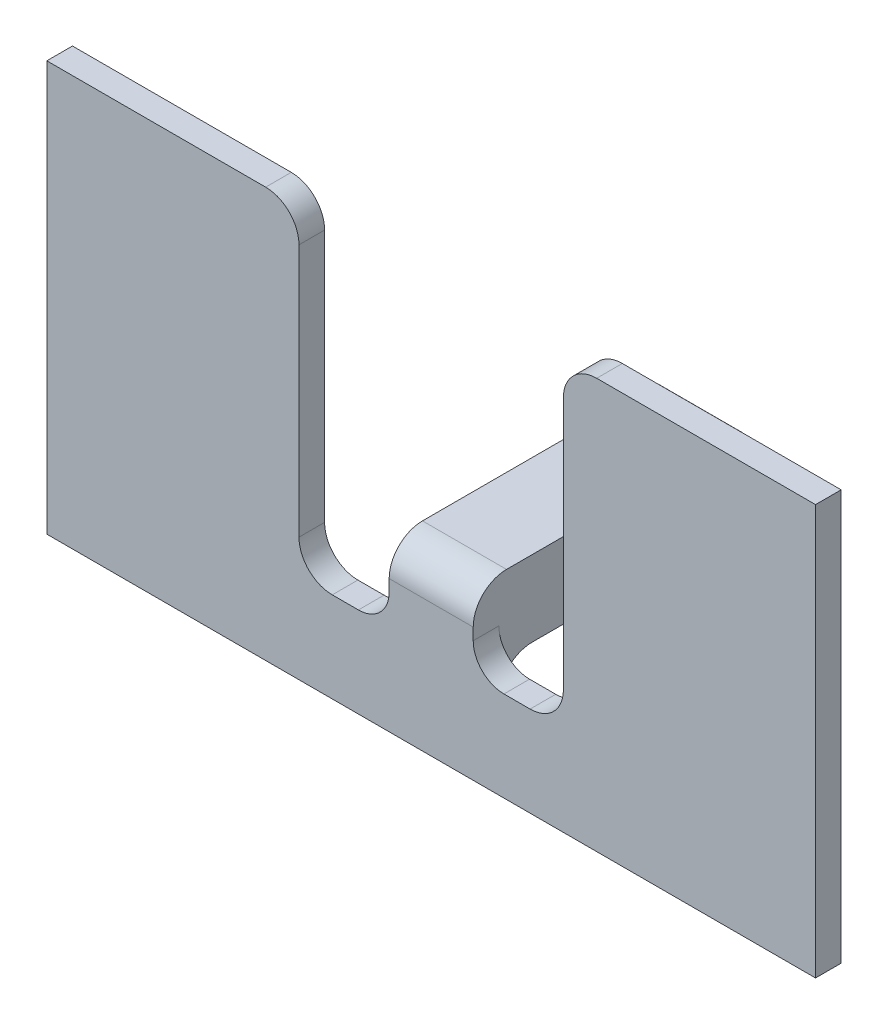
SolidWorks part; units mm, degrees
ref_plane "Front Plane" through (0, 0, 0) normal (0, 0, 1) x (1, 0, 0)
ref_plane "Top Plane" through (0, 0, 0) normal (0, 1, 0) x (1, 0, 0)
ref_plane "Right Plane" through (0, 0, 0) normal (1, 0, 0) x (0, 0, -1)
sketch "Sketch1" plane through (0, 0, 0) normal (0, 0, 1) x (1, 0, 0)
  line L0 (42.5, 135.506) -> (42.5, -16.894) construction
  line L1 (-37.5, -20) -> (37.5, -20)
  line L2 (-37.5, -20) -> (-37.5, 20)
  line L3 (-37.5, 20) -> (37.5, 20)
  line L4 (37.5, -20) -> (37.5, 20)
  line L5 (-37.5, -20) -> (37.5, 20) construction
  line L6 (-37.5, 20) -> (37.5, -20) construction
  point P1 (0, 0)
  point P6 (35.5594, 27.5)
  dimension "D1" = 5
  dimension "D2" = 40
extrude "Boss-Extrude1" add sketch "Sketch1" along normal blind 2.5
sketch "Sketch2" plane through (0, 0, 0) normal (0, 0, 1) x (1, 0, 0)
  line L0 (37.5, 20) -> (-37.5, 20) construction
  line L1 (12.9, 20) -> (-12.9, 20)
  line L2 (12.9, 20) -> (12.9, -11.2)
  line L3 (12.9, -11.2) -> (-12.9, -11.2)
  line L4 (-12.9, 20) -> (-12.9, -11.2)
  line L5 (-11.9, 0.4) -> (-11.9, -7.6) construction
  line L6 (4.1, -11.2) -> (-4.1, -11.2)
  line L7 (4.1, -11.2) -> (4.1, -3.8)
  line L8 (4.1, -3.8) -> (-4.1, -3.8)
  line L9 (-4.1, -11.2) -> (-4.1, -3.8)
  line L10 (4.9, -11.2) -> (11.9, -11.2) construction
  line L11 (-4.1, -4.4) -> (-4.1, -3.2) construction
  point P6 (0, 20)
  point P12 (0, -3.8)
  point P17 (-4.1, -3.8)
  dimension "D1" = 1
extrude "Cut-Extrude1" cut sketch "Sketch2" along normal blind 10 contours L3 L9 L8 L7 L2 L1 L4 region at (0, 5.3702, 0)
extrude "Boss-Extrude2" add sketch "Sketch2<3>" against normal up to surface (23.814 mm away) contours L9 L3 L7 L8 region at (0, -7.5, 0)
sketch "Sketch2<3>" plane through (0, 0, 0) normal (0, 0, 1) x (1, 0, 0) same geometry as "Sketch2"
fillet "Fillet1" radius 3.25 7 edges at (-12.9, 20, 1.25) (-12.9, -11.2, 1.25) (0, -3.8, 2.5) (0, -11.2, 0) (12.9, -11.2, 1.25) (12.9, 20, 1.25) (0, -11.2, -23.814)
fillet "Fillet2" radius 3 2 edges at (4.1, -11.2, 1.25) (-4.1, -11.2, 1.25)
